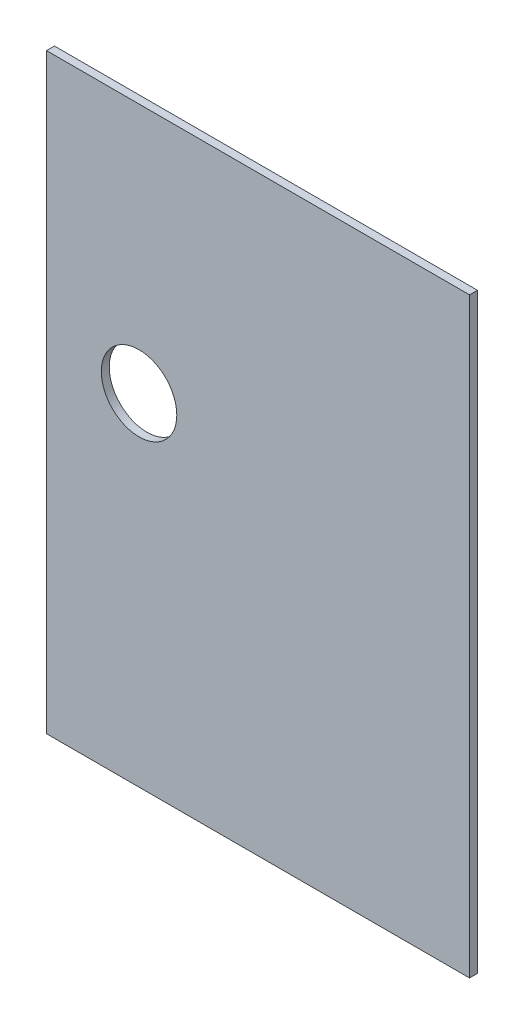
SolidWorks part; units mm, degrees
ref_plane "Front Plane" through (0, 0, 0) normal (0, 0, 1) x (1, 0, 0)
ref_plane "Top Plane" through (0, 0, 0) normal (0, 1, 0) x (1, 0, 0)
ref_plane "Right Plane" through (0, 0, 0) normal (1, 0, 0) x (0, 0, -1)
sketch "Sketch1" plane through (0, 0, 0) normal (0, 0, 1) x (1, 0, 0)
  line L1 (0, 0) -> (160, 0)
  line L2 (0, 0) -> (0, 223.74)
  line L3 (0, 223.74) -> (160, 223.74)
  line L4 (160, 0) -> (160, 223.74)
  dimension "D1" = 160
  dimension "D2" = 223.74
extrude "Boss-Extrude1" add sketch "Sketch1" along normal blind 3
sketch "Sketch2" plane through (0, 0, 3) normal (0, 0, 1) x (1, 0, 0)
  line L0 (160, 223.74) -> (0, 223.74) construction
  line L2 (0, 223.74) -> (0, 0) construction
  circle A0 centre (35, 129) radius 14.275
  dimension "D1" = 28.55
  dimension "D2" = 35
  dimension "D3" = 94.74
extrude "Cut-Extrude1" cut sketch "Sketch2" against normal blind 3
